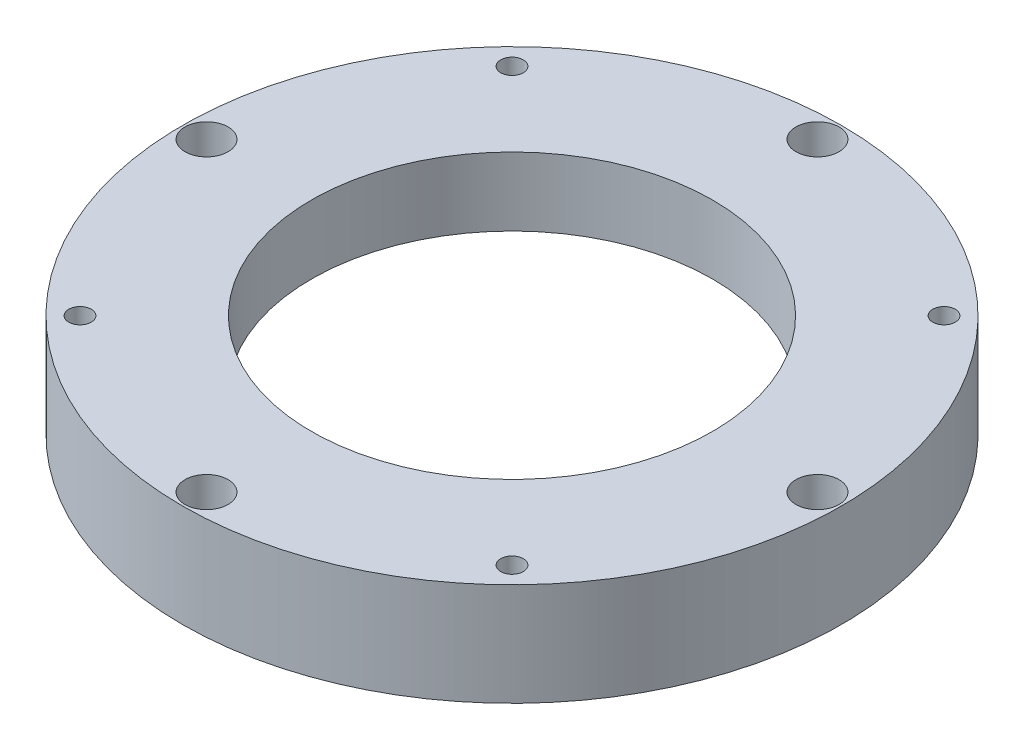
SolidWorks part; units mm, degrees
ref_plane "Front Plane" through (0, 0, 0) normal (0, 0, 1) x (1, 0, 0)
ref_plane "Top Plane" through (0, 0, 0) normal (0, 1, 0) x (1, 0, 0)
ref_plane "Right Plane" through (0, 0, 0) normal (1, 0, 0) x (0, 0, -1)
sketch "Sketch1" plane through (0, 0, 0) normal (0, 1, 0) x (1, 0, 0)
  line L0 (0, 0) -> (42.5, 0) construction
  circle A0 centre (0, 0) radius 45.85
  circle A1 centre (0, 0) radius 27.9
  circle A2 centre (42.5, 0) radius 1.5635
  circle A3 centre (30.052, -30.052) radius 1.5635
  circle A4 centre (0, -42.5) radius 1.5635
  circle A5 centre (0, 0) radius 40
  circle A6 centre (-30.052, -30.052) radius 1.5635
  circle A7 centre (-42.5, 0) radius 1.5635
  circle A8 centre (-30.052, 30.052) radius 1.5635
  circle A9 centre (0, 42.5) radius 1.5635
  circle A10 centre (30.052, 30.052) radius 1.5635
  point P13 (0, 0)
  dimension "D1" = 91.7
  dimension "D2" = 55.8
  dimension "D4" = 3.127
  dimension "D6" = 80
  dimension "D3" = 42.5
  dimension "D5" = 8
extrude "Boss-Extrude1" add sketch "Sketch1" against normal blind 4.7625 contours A0 A5 A2 A4 A3 region at (-44.5532, 0, 0)
extrude "Boss-Extrude2" add sketch "Sketch1<4>" along normal blind 4.7625 contours A1 A5 | A0 A5 A2 A4 A3 region at (-44.5532, 0, 0) region at (-38.8686, 0, 0)
sketch "Sketch1<4>" plane through (0, 0, 0) normal (0, 1, 0) x (1, 0, 0) same geometry as "Sketch1"
sketch "Sketch4" plane through (0, 4.7625, 0) normal (0, 1, 0) x (1, 0, 0)
  line L0 (28.4932, -27.352) -> (26.9343, -30.052)
  line L7 (30.052, 33.1697) -> (27.352, 31.6109)
  line L8 (27.352, 31.6109) -> (27.352, 28.4932)
  line L9 (27.352, 28.4932) -> (30.052, 26.9343)
  line L10 (30.052, 26.9343) -> (32.752, 28.4932)
  line L11 (32.752, 28.4932) -> (32.752, 31.6109)
  line L12 (32.752, 31.6109) -> (30.052, 33.1697)
  line L13 (31.6109, -27.352) -> (28.4932, -27.352)
  line L14 (33.1697, -30.052) -> (31.6109, -27.352)
  line L15 (31.6109, -32.752) -> (33.1697, -30.052)
  line L16 (28.4932, -32.752) -> (31.6109, -32.752)
  line L17 (26.9343, -30.052) -> (28.4932, -32.752)
  line L18 (-27.352, -28.4932) -> (-30.052, -26.9343)
  line L19 (-27.352, -31.6109) -> (-27.352, -28.4932)
  line L20 (-30.052, -33.1697) -> (-27.352, -31.6109)
  line L21 (-32.752, -31.6109) -> (-30.052, -33.1697)
  line L22 (-32.752, -28.4932) -> (-32.752, -31.6109)
  line L23 (-30.052, -26.9343) -> (-32.752, -28.4932)
  line L24 (-28.4932, 27.352) -> (-26.9343, 30.052)
  line L25 (-31.6109, 27.352) -> (-28.4932, 27.352)
  line L26 (-33.1697, 30.052) -> (-31.6109, 27.352)
  line L27 (-31.6109, 32.752) -> (-33.1697, 30.052)
  line L28 (-28.4932, 32.752) -> (-31.6109, 32.752)
  line L29 (-26.9343, 30.052) -> (-28.4932, 32.752)
  circle A0 centre (30.052, 30.052) radius 2.7 construction
  point P1 (31.402, 32.3903)
  point P32 (0, 0)
  dimension "D1" = 5.4
  dimension "D2" = 4
extrude "Cut-Extrude2" cut sketch "Sketch4" against normal blind 4.7625
sketch "Sketch3" plane through (0, 4.7625, 0) normal (0, 1, 0) x (1, 0, 0)
  circle A6 centre (0, -42.5) radius 1.5635 construction
  circle A7 centre (42.5, 0) radius 1.5635 construction
  circle A8 centre (0, 42.5) radius 1.5635 construction
  circle A9 centre (-42.5, 0) radius 1.5635 construction
  circle A10 centre (0, 0) radius 27.9 construction
  circle A11 centre (0, 0) radius 45.85 construction
  circle A12 centre (0, -42.5) radius 1.5635
  circle A13 centre (42.5, 0) radius 1.5635
  circle A14 centre (0, 42.5) radius 1.5635
  circle A15 centre (-42.5, 0) radius 1.5635
  circle A16 centre (0, 0) radius 27.9
  circle A17 centre (0, 0) radius 45.85
  circle A18 centre (0, 42.5) radius 3
  circle A19 centre (42.5, 0) radius 3
  circle A20 centre (0, -42.5) radius 3
  circle A21 centre (-42.5, 0) radius 3
  circle A22 centre (-30.052, 30.052) radius 1.565
  circle A23 centre (30.052, 30.052) radius 1.565
  circle A24 centre (30.052, -30.052) radius 1.565
  circle A25 centre (-30.052, -30.052) radius 1.565
  circle M1 centre (0, 0) radius 27.9
  circle M6 centre (0, 0) radius 45.85
  line M21 (-33.1697, 30.052) -> (-31.6109, 32.752)
  line M22 (-31.6109, 32.752) -> (-28.4932, 32.752)
  line M23 (-28.4932, 32.752) -> (-26.9343, 30.052)
  line M24 (-26.9343, 30.052) -> (-28.4932, 27.352)
  line M25 (-28.4932, 27.352) -> (-31.6109, 27.352)
  line M26 (-31.6109, 27.352) -> (-33.1697, 30.052)
  line M27 (-30.052, -33.1697) -> (-32.752, -31.6109)
  line M28 (-32.752, -31.6109) -> (-32.752, -28.4932)
  line M29 (-32.752, -28.4932) -> (-30.052, -26.9343)
  line M30 (-30.052, -26.9343) -> (-27.352, -28.4932)
  line M31 (-27.352, -28.4932) -> (-27.352, -31.6109)
  line M32 (-27.352, -31.6109) -> (-30.052, -33.1697)
  line M33 (33.1697, -30.052) -> (31.6109, -32.752)
  line M34 (31.6109, -32.752) -> (28.4932, -32.752)
  line M35 (28.4932, -32.752) -> (26.9343, -30.052)
  line M36 (26.9343, -30.052) -> (28.4932, -27.352)
  line M37 (28.4932, -27.352) -> (31.6109, -27.352)
  line M38 (31.6109, -27.352) -> (33.1697, -30.052)
  line M39 (30.052, 33.1697) -> (32.752, 31.6109)
  line M40 (32.752, 31.6109) -> (32.752, 28.4932)
  line M41 (32.752, 28.4932) -> (30.052, 26.9343)
  line M42 (30.052, 26.9343) -> (27.352, 28.4932)
  line M43 (27.352, 28.4932) -> (27.352, 31.6109)
  line M44 (27.352, 31.6109) -> (30.052, 33.1697)
  dimension "D1" = 6
  dimension "D2" = 3.13
extrude "Boss-Extrude3" add sketch "Sketch3" along normal blind 4.7625 contours A21 A20 A19 A18 M6 M1 M44 M39 M40 M41 M42 M43 M38 M33 M34 M35 M36 M37 M32 M27 M28 M29 M30 M31 M26 M21 M22 M23 M24 M25 | A22 M21 M26 M25 M24 M23 M22 | A23 M39 M44 M43 M42 M41 M40 | A24 M33 M38 M37 M36 M35 M34 | A25 M27 M32 M31 M30 M29 M28 region at (-45.7203, 4.7625, 0) region at (-32.3189, 4.7625, -31.3608) region at (-31.3608, 4.7625, 32.3189) region at (32.3189, 4.7625, 31.3608) region at (31.3608, 4.7625, -32.3189)
sketch "Sketch5" plane through (0, 9.525, 0) normal (0, 1, 0) x (1, 0, 0)
  line L0 (0, 0) -> (30.052, 30.052) construction
  circle A0 centre (0, 42.5) radius 3 construction
  circle A1 centre (30.052, 30.052) radius 1.565 construction
  circle A2 centre (42.5, 0) radius 3 construction
  circle A3 centre (30.052, -30.052) radius 1.565 construction
  circle A4 centre (0, -42.5) radius 3 construction
  circle A5 centre (-30.052, -30.052) radius 1.565 construction
  circle A6 centre (-42.5, 0) radius 3 construction
  circle A7 centre (-30.052, 30.052) radius 1.565 construction
  circle A8 centre (0, 0) radius 45.85 construction
  circle A9 centre (0, 0) radius 27.9 construction
  circle A10 centre (0, 42.5) radius 3
  circle A11 centre (30.052, 30.052) radius 1.565
  circle A12 centre (42.5, 0) radius 3
  circle A13 centre (30.052, -30.052) radius 1.565
  circle A14 centre (0, -42.5) radius 3
  circle A15 centre (-30.052, -30.052) radius 1.565
  circle A16 centre (-42.5, 0) radius 3
  circle A17 centre (-30.052, 30.052) radius 1.565
  circle A18 centre (0, 0) radius 45.85
  circle A19 centre (0, 0) radius 27.9
  arc A20 (6.31, 31.2697) -> (18.4511, 26.0224) centre (0, 0) cw
  arc A21 (4.6718, 37.2871) -> (6.4423, 39.762) centre (0, 42.5) ccw
  arc A22 (24.5734, 31.0284) -> (24.5119, 29.527) centre (30.052, 30.052) ccw
  arc A23 (24.5119, 29.527) -> (18.4511, 26.0224) centre (20.6784, 29.1636) cw
  arc A24 (4.6718, 37.2871) -> (6.31, 31.2697) centre (7, 34.6892) ccw
  arc A25 (22.8162, 35.0834) -> (24.5734, 31.0284) centre (20.6354, 31.7302) cw
  arc A26 (8.6987, 40.936) -> (6.4423, 39.762) centre (8.283, 38.9797) ccw
  arc A27 (22.8162, 35.0834) -> (8.6987, 40.936) centre (0, 0) ccw
  arc A28 (35.0834, 22.8162) -> (31.0284, 24.5734) centre (31.7302, 20.6354) ccw
  arc A29 (31.0284, 24.5734) -> (29.527, 24.5119) centre (30.052, 30.052) cw
  arc A30 (29.527, 24.5119) -> (26.0224, 18.4511) centre (29.1636, 20.6784) ccw
  arc A31 (31.2697, 6.31) -> (26.0224, 18.4511) centre (0, 0) ccw
  arc A32 (35.0834, 22.8162) -> (40.936, 8.6987) centre (0, 0) cw
  arc A33 (40.936, 8.6987) -> (39.762, 6.4423) centre (38.9797, 8.283) cw
  arc A34 (37.2871, 4.6718) -> (39.762, 6.4423) centre (42.5, 0) cw
  arc A35 (37.2871, 4.6718) -> (31.2697, 6.31) centre (34.6892, 7) cw
  arc A36 (37.2871, -4.6718) -> (31.2697, -6.31) centre (34.6892, -7) ccw
  arc A37 (31.2697, -6.31) -> (26.0224, -18.4511) centre (0, 0) cw
  arc A38 (29.527, -24.5119) -> (26.0224, -18.4511) centre (29.1636, -20.6784) cw
  arc A39 (31.0284, -24.5734) -> (29.527, -24.5119) centre (30.052, -30.052) ccw
  arc A40 (35.0834, -22.8162) -> (31.0284, -24.5734) centre (31.7302, -20.6354) cw
  arc A41 (35.0834, -22.8162) -> (40.936, -8.6987) centre (0, 0) ccw
  arc A42 (40.936, -8.6987) -> (39.762, -6.4423) centre (38.9797, -8.283) ccw
  arc A43 (37.2871, -4.6718) -> (39.762, -6.4423) centre (42.5, 0) ccw
  arc A44 (24.5119, -29.527) -> (18.4511, -26.0224) centre (20.6784, -29.1636) ccw
  arc A45 (24.5734, -31.0284) -> (24.5119, -29.527) centre (30.052, -30.052) cw
  arc A46 (22.8162, -35.0834) -> (24.5734, -31.0284) centre (20.6354, -31.7302) ccw
  arc A47 (22.8162, -35.0834) -> (8.6987, -40.936) centre (0, 0) cw
  arc A48 (6.31, -31.2697) -> (18.4511, -26.0224) centre (0, 0) ccw
  arc A49 (4.6718, -37.2871) -> (6.31, -31.2697) centre (7, -34.6892) cw
  arc A50 (4.6718, -37.2871) -> (6.4423, -39.762) centre (0, -42.5) cw
  arc A51 (8.6987, -40.936) -> (6.4423, -39.762) centre (8.283, -38.9797) cw
  arc A52 (-4.6718, -37.2871) -> (-6.31, -31.2697) centre (-7, -34.6892) ccw
  arc A53 (-6.31, -31.2697) -> (-18.4511, -26.0224) centre (0, 0) cw
  arc A54 (-24.5119, -29.527) -> (-18.4511, -26.0224) centre (-20.6784, -29.1636) cw
  arc A55 (-24.5734, -31.0284) -> (-24.5119, -29.527) centre (-30.052, -30.052) ccw
  arc A56 (-22.8162, -35.0834) -> (-24.5734, -31.0284) centre (-20.6354, -31.7302) cw
  arc A57 (-22.8162, -35.0834) -> (-8.6987, -40.936) centre (0, 0) ccw
  arc A58 (-8.6987, -40.936) -> (-6.4423, -39.762) centre (-8.283, -38.9797) ccw
  arc A59 (-4.6718, -37.2871) -> (-6.4423, -39.762) centre (0, -42.5) ccw
  arc A60 (-29.527, -24.5119) -> (-26.0224, -18.4511) centre (-29.1636, -20.6784) ccw
  arc A61 (-31.0284, -24.5734) -> (-29.527, -24.5119) centre (-30.052, -30.052) cw
  arc A62 (-35.0834, -22.8162) -> (-31.0284, -24.5734) centre (-31.7302, -20.6354) ccw
  arc A63 (-35.0834, -22.8162) -> (-40.936, -8.6987) centre (0, 0) cw
  arc A64 (-31.2697, -6.31) -> (-26.0224, -18.4511) centre (0, 0) ccw
  arc A65 (-37.2871, -4.6718) -> (-31.2697, -6.31) centre (-34.6892, -7) cw
  arc A66 (-37.2871, -4.6718) -> (-39.762, -6.4423) centre (-42.5, 0) cw
  arc A67 (-40.936, -8.6987) -> (-39.762, -6.4423) centre (-38.9797, -8.283) cw
  arc A68 (-37.2871, 4.6718) -> (-31.2697, 6.31) centre (-34.6892, 7) ccw
  arc A69 (-31.2697, 6.31) -> (-26.0224, 18.4511) centre (0, 0) cw
  arc A70 (-29.527, 24.5119) -> (-26.0224, 18.4511) centre (-29.1636, 20.6784) cw
  arc A71 (-31.0284, 24.5734) -> (-29.527, 24.5119) centre (-30.052, 30.052) ccw
  arc A72 (-35.0834, 22.8162) -> (-31.0284, 24.5734) centre (-31.7302, 20.6354) cw
  arc A73 (-35.0834, 22.8162) -> (-40.936, 8.6987) centre (0, 0) ccw
  arc A74 (-40.936, 8.6987) -> (-39.762, 6.4423) centre (-38.9797, 8.283) ccw
  arc A75 (-37.2871, 4.6718) -> (-39.762, 6.4423) centre (-42.5, 0) ccw
  arc A76 (-24.5119, 29.527) -> (-18.4511, 26.0224) centre (-20.6784, 29.1636) ccw
  arc A77 (-24.5734, 31.0284) -> (-24.5119, 29.527) centre (-30.052, 30.052) cw
  arc A78 (-22.8162, 35.0834) -> (-24.5734, 31.0284) centre (-20.6354, 31.7302) ccw
  arc A79 (-22.8162, 35.0834) -> (-8.6987, 40.936) centre (0, 0) cw
  arc A80 (-6.31, 31.2697) -> (-18.4511, 26.0224) centre (0, 0) ccw
  arc A81 (-4.6718, 37.2871) -> (-6.31, 31.2697) centre (-7, 34.6892) cw
  arc A82 (-4.6718, 37.2871) -> (-6.4423, 39.762) centre (0, 42.5) cw
  arc A83 (-8.6987, 40.936) -> (-6.4423, 39.762) centre (-8.283, 38.9797) cw
  point P137 (0, 0)
  dimension "D1" = 4
  dimension "D2" = 4
  dimension "D3" = 4
  dimension "D4" = 4
  dimension "D5" = 12
  dimension "D8" = 2
  dimension "D9" = 4
  dimension "D7" = 14
  dimension "D6" = 4
extrude "Cut-Extrude3" [suppressed] cut sketch "Sketch5" against normal blind 4.7625 contours A75 A68 A69 A70 A71 A72 A73 A74 | A83 A79 A78 A77 A76 A80 A81 A82 | A25 A27 A26 A21 A24 A20 A23 A22 | A35 A34 A33 A32 A28 A29 A30 A31 | A43 A36 A37 A38 A39 A40 A41 A42 | A51 A47 A46 A45 A44 A48 A49 A50 | A59 A52 A53 A54 A55 A56 A57 A58 | A67 A63 A62 A61 A60 A64 A65 A66
equation "\"bearing_21_OD\"= 21mm"
equation "\"pin_cirlce_diameter\"= 75mm"
equation "\"pin_diam\"= 6mm"
equation "\"gear_thickness\"= 4mm"
equation "\"ball_bearing_diam\"= 3.214mm"
equation "\"bearing_21_outer_clearance\"= 0.127mm'change this"
equation "\"bearing_15_OD\"= 15mm"
equation "\"bearing_15_outer_clearance\"= 0mm'change this"
equation "\"thrust_bearing_thickness\"= 5mm'measure this irl and change"
equation "\"D1@Boss-Extrude1\"=\"sheetThickness\""
equation "\"largeBearOD\"= 21mm"
equation "\"largeBearID\" = 15mm"
equation "\"largeBearOTight\"= 0.28mm'calibrate - hold onto gears"
equation "\"largeBearITight\"= 0mm'calibrate - hold onto eccentric nut"
equation "\"largeBearFlangeDiam\" = 22.5mm"
equation "\"largeBearFlangeWidth\" = 0.8mm"
equation "\"smallBearOD\"= 15mm"
equation "\"smallBearOTight\"= 0.2mm'calibrate - hold onto bottom of gearbox"
equation "\"smallBearOLoose\"= 0mm'calibrate - able to take off topHat"
equation "\"smallBearID\" = 10mm"
equation "\"smallBearITight\" = 0mm'hold onto "
equation "\"pinCircleDiam\"= 75mm"
equation "\"pinDiam\"= 6mm"
equation "\"sheetThickness\"= 0.1875in"
equation "\"ballBearDiam\"= 3.5mm"
equation "\"thrustBearingThickness\"= 5mm'measure this irl and change"
equation "\"thrustBearingID\"= 0mm'measure this irl and change"
equation "\"thrustBearingOD\"= 0mm'measure this irl and change"
equation "\"eccentricity\" = 1mm"
equation "\"D1@Boss-Extrude2\"=\"sheetThickness\""
equation "\"D1@Boss-Extrude3\"=\"sheetThickness\""
equation "\"D1@Cut-Extrude2\"=\"sheetThickness\""
equation "\"D1@Cut-Extrude3\"=\"sheetThickness\""
